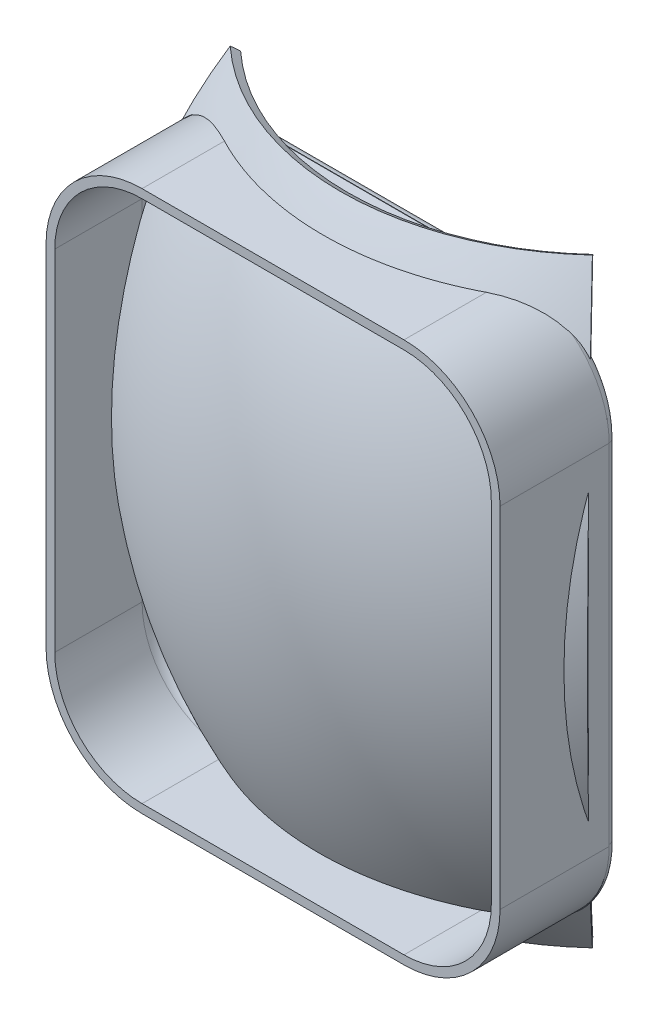
SolidWorks part; units mm, degrees
ref_plane "Front Plane" through (0, 0, 0) normal (0, 0, 1) x (1, 0, 0)
ref_plane "Top Plane" through (0, 0, 0) normal (0, 1, 0) x (1, 0, 0)
ref_plane "Right Plane" through (0, 0, 0) normal (1, 0, 0) x (0, 0, -1)
sketch "Wall Backing" plane through (0, 0, 0) normal (0, 0, 1) x (1, 0, 0)
  line L1 (-37.5, 55) -> (37.5, 55)
  line L2 (-37.5, 55) -> (-37.5, -55)
  line L3 (-37.5, -55) -> (37.5, -55)
  line L4 (37.5, 55) -> (37.5, -55)
  line L5 (-28.5, 50) -> (28.5, 50)
  line L6 (-28.5, 50) -> (-28.5, -50)
  line L7 (-28.5, -50) -> (28.5, -50)
  line L8 (28.5, 50) -> (28.5, -50)
  point P4 (-37.5, 0)
  point P6 (0, 55)
  point P11 (0, 50)
  point P12 (-28.5, 0)
  dimension "D1" = 75
  dimension "D2" = 110
  dimension "D3" = 57
  dimension "D4" = 100
sketch "Case Sides" plane through (0, 0, 0) normal (0, 0, 1) x (1, 0, 0)
  line L0 (0, 60) -> (0, -60) construction
  line L5 (-30, 60) -> (30, 60)
  line L6 (-50, 40) -> (-50, -40)
  line L7 (-30, -60) -> (30, -60)
  line L8 (50, 40) -> (50, -40)
  line L9 (-50, 0) -> (50, 0) construction
  line L10 (-30, 62) -> (30, 62)
  line L11 (52, 40) -> (52, -40)
  line L12 (-30, -62) -> (30, -62)
  line L13 (-52, 40) -> (-52, -40)
  arc A2 (50, 40) -> (30, 60) centre (30, 40) ccw
  arc A3 (50, -40) -> (30, -60) centre (30, -40) cw
  arc A4 (-30, -60) -> (-50, -40) centre (-30, -40) cw
  arc A5 (-50, 40) -> (-30, 60) centre (-30, 40) cw
  arc A6 (52, 40) -> (30, 62) centre (30, 40) ccw
  arc A7 (52, -40) -> (30, -62) centre (30, -40) cw
  arc A8 (-30, -62) -> (-52, -40) centre (-30, -40) cw
  arc A9 (-52, 40) -> (-30, 62) centre (-30, 40) cw
  point P17 (50, 60)
  point P23 (-50, -60)
  point P26 (-50, 60)
  dimension "D5" = 20
  dimension "D3" = 100
  dimension "D4" = 120
  dimension "D6" = 2
sketch "Case Bottom" plane through (0, 0, 0) normal (0, 0, 1) x (1, 0, 0)
  line L0 (-30.1664, 62.1012) -> (30.1664, 62.1012)
  line L1 (51.8136, 39.8409) -> (51.8136, -39.8409)
  line L2 (-30.2679, -61.8723) -> (30.2679, -61.8723)
  line L3 (-52.1862, 40.0195) -> (-52.1862, -40.0195)
  line L4 (0, 41) -> (0, 0) construction
  line L5 (0, 0) -> (0, -41) construction
  line L6 (0, -30) -> (0, 0) construction
  line L7 (0, 30) -> (0, 0) construction
  arc A0 (51.8136, 39.8409) -> (30.1664, 62.1012) centre (29.8858, 40.1727) ccw
  arc A1 (51.8136, -39.8409) -> (30.2679, -61.8723) centre (30.6332, -40.6785) cw
  arc A2 (-30.2679, -61.8723) -> (-52.1862, -40.0195) centre (-30.5767, -40.2636) cw
  arc A3 (-52.1862, 40.0195) -> (-30.1664, 62.1012) centre (-29.8045, 39.7205) cw
  circle A4 centre (0, 41) radius 1.75
  circle A5 centre (0, -41) radius 1.75
  circle A6 centre (0, 30) radius 5
  circle A7 centre (0, -30) radius 5
  point P21 (0, 0)
  point P22 (0, 0)
  point P23 (0, 62.1012)
  point P24 (0, -61.8723)
  point P25 (-52.1862, 0)
  point P26 (51.8136, 0)
  point P28 (0, 0)
  point P29 (0, 0)
  dimension "D2" = 3.5
  dimension "D3" = 10
  dimension "D1" = 82
  dimension "D4" = 30
  dimension "D5" = 104
extrude "Boss-Extrude7" add sketch "Case Sides" along normal blind 25
extrude "Boss-Extrude9" add sketch "Case Bottom" against normal blind 2
sketch "Sonoff" plane through (0, 0, 0) normal (0, 0, 1) x (1, 0, 0)
  line L0 (-44.5, -20) -> (-44.5, 20)
  line L1 (-44.5, -20) -> (44.5, -20)
  line L2 (44.5, -20) -> (44.5, 20)
  line L3 (-44.5, 20) -> (44.5, 20)
  line L4 (-44.5, 0) -> (44.5, 0) construction
  line L5 (0, 20) -> (0, -20) construction
  line L6 (-38, 16.75) -> (-38, 0) construction
  line L7 (38, -16.75) -> (38, 0) construction
  line L8 (-38, 16.75) -> (0, 16.75) construction
  line L9 (38, -16.75) -> (0, -16.75) construction
  circle A3 centre (-38, 16.75) radius 1
  circle A4 centre (38, -16.75) radius 1
  dimension "D5" = 2
  dimension "D1" = 89
  dimension "D2" = 40
  dimension "D3" = 76
  dimension "D4" = 33.5
fillet "Fillet1" radius 5 8 edges at (0, -60, 0) (-44.1421, -54.1421, 0) (-50, 0, 0) (-44.1421, 54.1421, 0) (0, 60, 0) (44.1421, 54.1421, 0) (50, 0, 0) (44.1421, -54.1421, 0)
fillet "Fillet2" radius 2 8 edges at (51.8136, 0, -2) (45.6079, 55.4618, -2) (0, 62.1012, -2) (-45.6544, 55.5259, -2) (45.7878, -55.4991, -2) (0, -61.8723, -2) (-45.835, -55.5677, -2) (-52.1862, 0, -2)
fillet "Fillet3" radius 1 8 edges at (1.75, -41, -2) (1.75, -41, 0) (5, -30, -2) (5, -30, 0) (5, 30, 0) (5, 30, -2) (1.75, 41, 0) (1.75, 41, -2)
extrude "Boss-Extrude10" add sketch "Sonoff" along normal blind 13
sketch "Sketch2" plane through (0, 0, 0) normal (0, 0, 1) x (1, 0, 0)
  line L0 (-23.5, -20) -> (-23.5, 20)
  line L1 (-23.5, -20) -> (23.5, -20)
  line L2 (23.5, -20) -> (23.5, 20)
  line L3 (-23.5, 20) -> (23.5, 20)
  point P4 (0, 20)
  point P5 (0, -20)
  dimension "D2" = 40
  dimension "D3" = 47
extrude "Boss-Extrude11" add sketch "Sketch2" along normal blind 24
sketch "Case Top" plane through (0, 0, 25) normal (0, 0, 1) x (1, 0, 0)
  line L0 (0, 60) -> (0, -60) construction
  line L1 (-30, 60) -> (30, 60)
  line L2 (-50, 40) -> (-50, -40)
  line L3 (-30, -60) -> (30, -60)
  line L4 (50, 40) -> (50, -40)
  line L5 (-50, 0) -> (50, 0) construction
  line L6 (-30, 62) -> (30, 62)
  line L7 (52, 40) -> (52, -40)
  line L8 (-30, -62) -> (30, -62)
  line L9 (-52, 40) -> (-52, -40)
  arc A0 (50, 40) -> (30, 60) centre (30, 40) ccw
  arc A1 (50, -40) -> (30, -60) centre (30, -40) cw
  arc A2 (-30, -60) -> (-50, -40) centre (-30, -40) cw
  arc A3 (-50, 40) -> (-30, 60) centre (-30, 40) cw
  arc A4 (52, 40) -> (30, 62) centre (30, 40) ccw
  arc A5 (52, -40) -> (30, -62) centre (30, -40) cw
  arc A6 (-30, -62) -> (-52, -40) centre (-30, -40) cw
  arc A7 (-52, 40) -> (-30, 62) centre (-30, 40) cw
sketch "Cap Top/Bot" plane through (0, 0, 0) normal (0, 1, 0) x (1, 0, 0)
  arc A0 (-54.9354, -7.8818) -> (54.9354, -7.8818) centre (0, 51.5283) ccw
  point P3 (-60.6211, -12.4304)
  point P4 (0, -29.3881)
  point P6 (-54.9354, -7.8818)
  point P7 (0, 0)
  point P8 (0, 0)
sketch "Cap Sides" plane through (0, 0, 0) normal (1, 0, 0) x (0, 0, -1)
  line L0 (-9.5687, -68.7189) -> (-7.8742, -67.6566)
  line L1 (-9.5687, 68.7189) -> (-7.8742, 67.6566)
  arc A0 (-7.8742, 67.6566) -> (-7.8742, -67.6566) centre (100.0545, 0) ccw
  arc A1 (-9.5687, 68.7189) -> (-9.5687, -68.7189) centre (100.0545, 0) ccw
  point P4 (-27.3269, 0)
  dimension "D1" = 2
surface "Surface-Sweep1"
